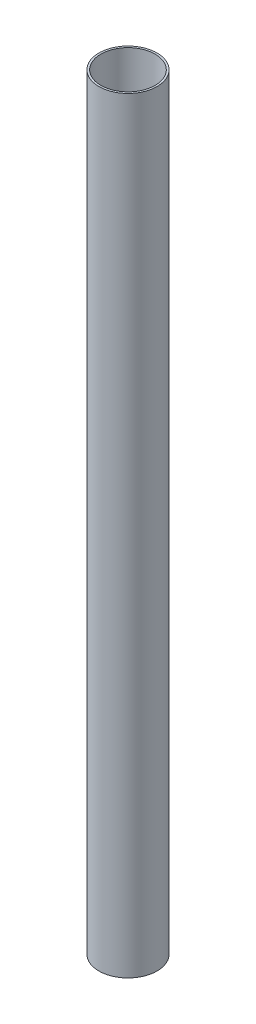
SolidWorks part; units mm, degrees
material "E-Glass Fiber"
ref_plane "Front Plane" through (0, 0, 0) normal (0, 0, 1) x (1, 0, 0)
ref_plane "Top Plane" through (0, 0, 0) normal (0, 1, 0) x (1, 0, 0)
ref_plane "Right Plane" through (0, 0, 0) normal (1, 0, 0) x (0, 0, -1)
sketch "Sketch1" plane through (0, 0, 0) normal (0, 0, 1) x (1, 0, 0)
  line L0 (0, 0) -> (0, -40.98) construction
  line L1 (28.9179, 50.986) -> (28.9179, -711.014) construction
  line L2 (26.9875, 50.986) -> (28.9179, 50.986)
  line L3 (26.9875, 50.986) -> (26.9875, -711.014)
  line L4 (26.9875, -711.014) -> (28.9179, -711.014)
  line L5 (28.9179, 50.986) -> (28.9179, -711.014)
revolve "Revolve1" add sketch "Sketch1" angle 360 about L0
